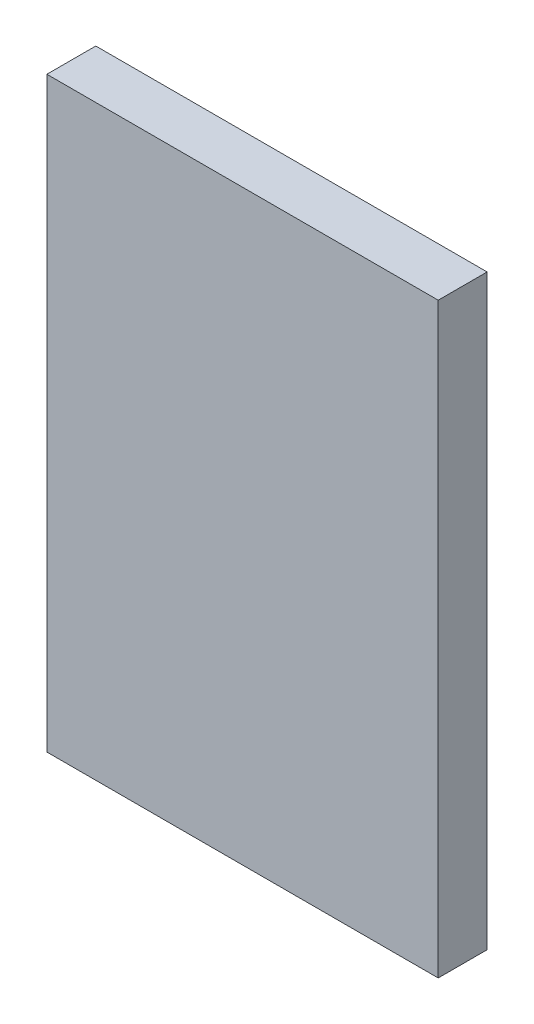
SolidWorks part; units mm, degrees
ref_plane "Front Plane" through (0, 0, 0) normal (0, 0, 1) x (1, 0, 0)
ref_plane "Top Plane" through (0, 0, 0) normal (0, 1, 0) x (1, 0, 0)
ref_plane "Right Plane" through (0, 0, 0) normal (1, 0, 0) x (0, 0, -1)
sketch "Sketch1" plane through (0, 0, 0) normal (0, 0, 1) x (1, 0, 0)
  line L1 (-19.6138, 16.2133) -> (20.3862, 16.2133)
  line L2 (-19.6138, 16.2133) -> (-19.6138, -43.7867)
  line L3 (-19.6138, -43.7867) -> (20.3862, -43.7867)
  line L4 (20.3862, 16.2133) -> (20.3862, -43.7867)
  dimension "D1" = 40
  dimension "D2" = 60
extrude "Boss-Extrude1" add sketch "Sketch1" along normal blind 5
sketch "Sketch4" plane through (0, 0, 0) normal (0, 0, -1) x (-1, 0, 0)
  line L0 (-0.3862, -28.7867) -> (-0.3862, 49971.2133) construction
  line L3 (19.6138, -43.7867) -> (-20.3862, -43.7867) construction
  line L4 (-15.3862, -13.7867) -> (49984.6138, -13.7867) construction
  line L5 (-20.3862, -43.7867) -> (-20.3862, 16.2133) construction
  line L6 (-0.3862, -3.5582) -> (-0.3862, -24.0153) construction
  line L7 (12.8992, -3.5582) -> (12.8992, -24.0153)
  line L8 (-13.6716, -3.5582) -> (-13.6716, -24.0153)
  line L9 (10.3992, -3.5582) -> (10.3992, -24.0153)
  line L10 (-11.1716, -3.5582) -> (-11.1716, -24.0153)
  arc A0 (12.8992, -3.5582) -> (-13.6716, -3.5582) centre (-0.3862, -3.5582) ccw
  arc A1 (-13.6716, -24.0153) -> (12.8992, -24.0153) centre (-0.3862, -24.0153) ccw
  arc A2 (-11.1716, -24.0153) -> (10.3992, -24.0153) centre (-0.3862, -24.0153) ccw
  arc A3 (10.3992, -3.5582) -> (-11.1716, -3.5582) centre (-0.3862, -3.5582) ccw
  point P4 (-0.3862, -43.7867)
  point P9 (-20.3862, -13.7867)
  point P12 (-0.3862, -13.7867)
  dimension "D1" = 2.5
extrude "Boss-Extrude2" add sketch "Sketch4" along normal blind 6.35
